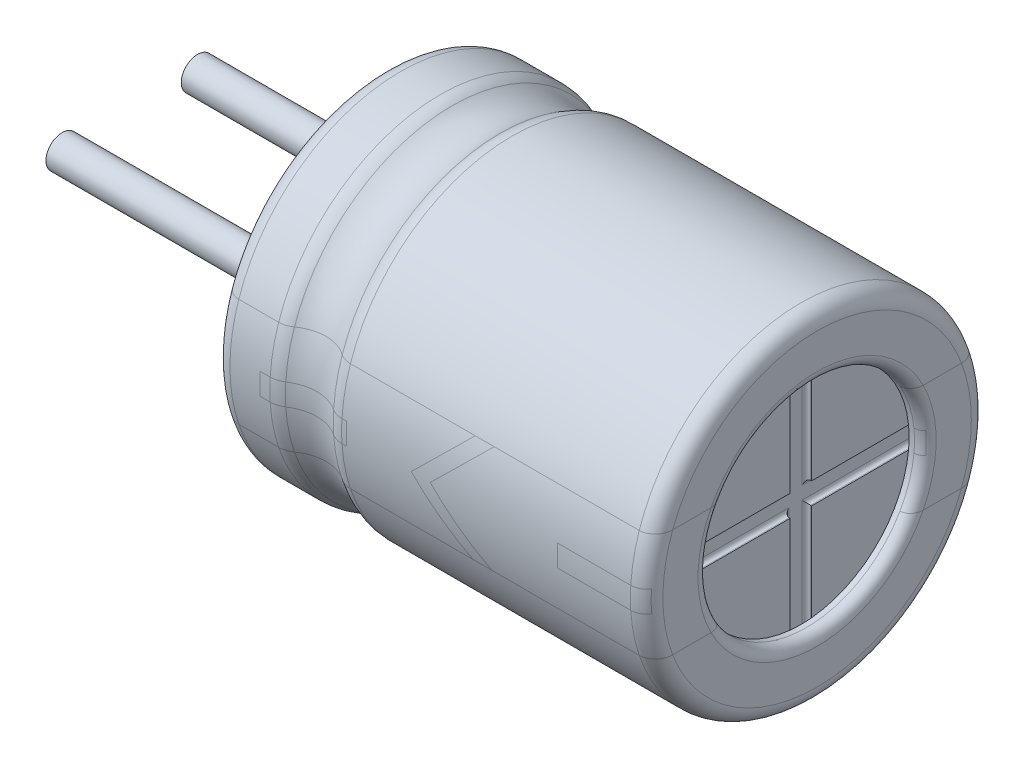
SolidWorks part; units mm, degrees
ref_plane "Front Plane" through (0, 0, 0) normal (0, 0, 1) x (1, 0, 0)
ref_plane "Top Plane" through (0, 0, 0) normal (0, 1, 0) x (1, 0, 0)
ref_plane "Right Plane" through (0, 0, 0) normal (1, 0, 0) x (0, 0, -1)
sketch "Эскиз1" plane through (0, 0, 0) normal (0, 1, 0) x (1, 0, 0)
  line L0 (-17.2337, 0) -> (16.838, 0) construction
  line L1 (0, 0) -> (0, 3.15)
  line L2 (0, 3.15) -> (1.1708, 3.15)
  line L3 (8, 3.15) -> (8, 0)
  line L4 (8, 0) -> (0, 0)
  line L5 (2.2292, 3.15) -> (8, 3.15)
  arc A0 (1.1708, 3.15) -> (2.2292, 3.15) centre (1.7, 3.75) ccw
  dimension "D3" = 1.6
  dimension "D1" = 3.15
  dimension "D2" = 8
  dimension "D4" = 1.7
  dimension "D5" = 0.6
revolve "Повернуть1" add sketch "Эскиз1" angle 360 about L0
fillet "Скругление1" radius 0.4 2 edges at (2.2292, 0, 3.15) (1.1708, 0, 3.15)
sketch "Эскиз2" plane through (8, 0, 0) normal (1, 0, 0) x (0, 0, -1)
  line L0 (0, 3.4063) -> (0, -3.6242) construction
  line L1 (-3.4972, 0) -> (3.5584, 0) construction
  circle A0 centre (0, 0) radius 2
  dimension "D1" = 4
extrude "Вырез-Вытянуть1" cut sketch "Эскиз2" against normal blind 0.3
fillet "Скругление2" radius 0.2 1 edges at (8, 0, -2)
fillet "Скругление3" radius 0.3 1 edges at (8, 0, 3.15)
sketch "Эскиз3" plane through (7.7, 0, 0) normal (1, 0, 0) x (0, 0, -1)
  line L0 (0, 3.4147) -> (0, -3.4901) construction
  line L1 (-3.5223, 0) -> (3.4327, 0) construction
  line L2 (-0.2, 2.3648) -> (-0.2, 0.2)
  line L3 (-0.2, 0.2) -> (-2.3648, 0.2)
  line L4 (0.2, 0.2) -> (2.3648, 0.2)
  line L5 (0.2, 2.3648) -> (0.2, 0.2)
  line L6 (0.2, -0.2) -> (2.3648, -0.2)
  line L7 (0.2, -2.3648) -> (0.2, -0.2)
  line L8 (-0.2, -2.3648) -> (-0.2, -0.2)
  line L9 (-0.2, -0.2) -> (-2.3648, -0.2)
  circle A0 centre (0, 0) radius 2.3732 construction
  arc A1 (-2.3648, 0.2) -> (-2.3648, -0.2) centre (0, 0) ccw
  arc A2 (0.2, 2.3648) -> (-0.2, 2.3648) centre (0, 0) ccw
  arc A3 (2.3648, -0.2) -> (2.3648, 0.2) centre (0, 0) ccw
  arc A4 (-0.2, -2.3648) -> (0.2, -2.3648) centre (0, 0) ccw
  dimension "D1" = 0.2
  dimension "D2" = 0.2
extrude "Вырез-Вытянуть2" cut sketch "Эскиз3" against normal blind 0.1
sketch "Эскиз5" plane through (0, 0, 0) normal (-1, 0, 0) x (0, 0, 1)
  circle A0 centre (0, 0) radius 2
  dimension "D1" = 4
extrude "Вырез-Вытянуть3" cut sketch "Эскиз5" against normal blind 0.3
fillet "Скругление6" radius 0.3 2 edges at (0, 0, 2) (0, 0, 3.15)
sketch "Эскиз6" plane through (0.3, 0, 0) normal (-1, 0, 0) x (0, 0, 1)
  line L0 (-3.5152, 0) -> (3.4398, 0) construction
  line L1 (0, 3.3812) -> (0, -3.3644) construction
  circle A0 centre (-1.25, 0) radius 0.3
  circle A1 centre (1.25, 0) radius 0.3
  dimension "D1" = 0.6
  dimension "D2" = 1.25
extrude "Бобышка-Вытянуть1" add sketch "Эскиз6" along normal blind 5
fillet "Скругление7" radius 0.08 8 edges at (7.6, 1.2824, -0.2) (7.6, -1.2824, -0.2) (7.6, -0.2, -1.2824) (7.6, -0.2, 1.2824) (7.6, -1.2824, 0.2) (7.6, 1.2824, 0.2) (7.6, 0.2, -1.2824) (7.6, 0.2, 1.2824)
ref_plane "Плоскость1" through (0, 0, 3.5) normal (0, 0, 1) x (1, 0, 0)
sketch "Эскиз7" plane through (0, 0, 3.5) normal (0, 0, 1) x (1, 0, 0)
  line L0 (-2.8406, 0) -> (14.5012, 0) construction
  line L1 (0, 2.85) -> (0, -2.85) construction
  line L2 (-2, 1) -> (13, 1)
  line L3 (-2, 1) -> (-2, -1)
  line L4 (-2, -1) -> (13, -1)
  line L5 (13, 1) -> (13, -1)
  line L6 (10.5206, 1) -> (9.5, 0)
  line L7 (9.5, 0) -> (10.4798, -1)
  line L8 (10.4798, -1) -> (10.1298, -1)
  line L9 (10.1298, -1) -> (9.15, 0)
  line L10 (9.15, 0) -> (10.1706, 1)
  line L11 (10.1706, 1) -> (10.5206, 1)
  line L12 (4.6706, 1) -> (5.0206, 1)
  line L13 (6.35, 0.2) -> (7.95, 0.2)
  line L14 (6.35, 0.2) -> (6.35, -0.2)
  line L15 (6.35, -0.2) -> (7.95, -0.2)
  line L16 (7.95, 0.2) -> (7.95, -0.2)
  line L17 (6.35, 0.2) -> (7.95, -0.2) construction
  line L18 (6.35, -0.2) -> (7.95, 0.2) construction
  line L21 (4.9798, -1) -> (4.6298, -1)
  line L28 (-0.8294, 1) -> (-0.4794, 1)
  line L31 (-0.5202, -1) -> (-0.8702, -1)
  line L34 (-4.65, 0.2) -> (-4.65, -0.2)
  line L35 (-4.65, 0.2) -> (-3.05, 0.2)
  line L36 (-3.05, 0.2) -> (-3.05, -0.2)
  line L37 (-4.65, -0.2) -> (-3.05, -0.2)
  line L38 (-0.8702, -1) -> (-1.85, 0) [skipped]
  line L39 (-1.5, 0) -> (-0.5202, -1) [skipped]
  line L40 (-0.4794, 1) -> (-1.5, 0) [skipped]
  line L41 (-1.85, 0) -> (-0.8294, 1) [skipped]
  line L42 (0.85, 0.2) -> (0.85, -0.2) [skipped]
  line L43 (0.85, -0.2) -> (2.45, -0.2) [skipped]
  line L44 (2.45, 0.2) -> (2.45, -0.2) [skipped]
  line L45 (0.85, 0.2) -> (2.45, 0.2) [skipped]
  line L46 (4.6298, -1) -> (3.65, 0) [skipped]
  line L47 (4, 0) -> (4.9798, -1) [skipped]
  line L48 (5.0206, 1) -> (4, 0) [skipped]
  line L49 (3.65, 0) -> (4.6706, 1) [skipped]
  line L50 (0.85, 0.2) -> (0.85, -0.2)
  line L51 (0.85, 0.2) -> (2.45, 0.2)
  line L52 (2.45, 0.2) -> (2.45, -0.2)
  line L53 (0.85, -0.2) -> (2.45, -0.2)
  line L54 (4.6706, 1) -> (5.0206, 1)
  line L55 (5.0206, 1) -> (4, 0)
  line L56 (4, 0) -> (4.9798, -1)
  line L57 (4.9798, -1) -> (4.6298, -1)
  line L58 (4.6298, -1) -> (3.65, 0)
  line L59 (3.65, 0) -> (4.6706, 1)
  point P9 (13, 0)
  point P12 (7.15, 0)
  dimension "D1" = 15
  dimension "D2" = 2
  dimension "D3" = 2
  dimension "D4" = 0.25
  dimension "D5" = 3.5
  dimension "D6" = 1.4
  dimension "D7" = 1.6
  dimension "D8" = 0.4
  dimension "D9" = 1.2
  dimension "D10" = 3
  dimension "D11" = 2
split line "Разделяющая линия1"
